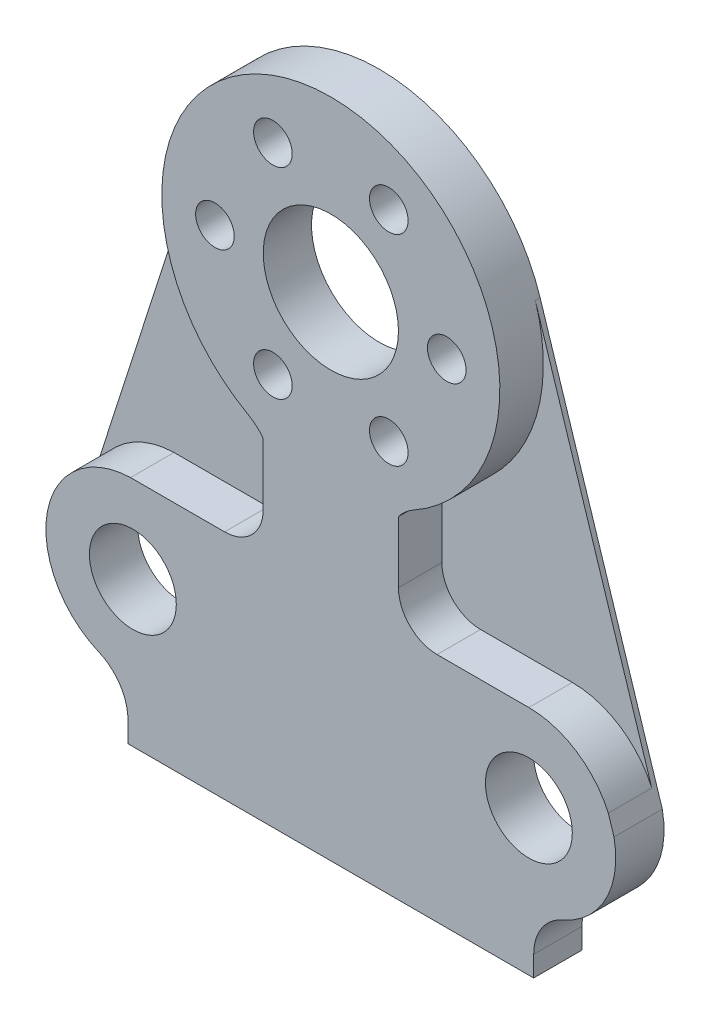
SolidWorks part; units mm, degrees
ref_plane "Front Plane" through (0, 0, 0) normal (0, 0, 1) x (1, 0, 0)
ref_plane "Top Plane" through (0, 0, 0) normal (0, 1, 0) x (1, 0, 0)
ref_plane "Right Plane" through (0, 0, 0) normal (1, 0, 0) x (0, 0, -1)
sketch "Sketch1" plane through (0, 0, 0) normal (0, 0, 1) x (1, 0, 0)
  line L0 (0, 0) -> (0, 50000) construction
  line L1 (-41, -72) -> (41, -72) construction
  line L6 (-41.4693, -54) -> (-22, -54)
  line L8 (21.4626, -54) -> (41, -54)
  line L9 (33.3347, 10.6675) -> (58.6345, -68.391)
  line L11 (-42, -97.7554) -> (-42, -102)
  line L12 (-42, -102) -> (42, -102)
  line L13 (42, -97.7488) -> (42, -102)
  line L14 (-33.3347, 10.6675) -> (-58.1419, -66.4886)
  line L15 (-13.9318, -32.1077) -> (13.9318, -32.1077) construction
  line L16 (-14, -33.2556) -> (-14, -46)
  line L17 (14, -33.2556) -> (14, -46)
  circle A0 centre (0, 0) radius 35
  circle A1 centre (0, 0) radius 14
  circle A2 centre (0, 0) radius 24 construction
  circle A3 centre (24, 0) radius 4
  circle A4 centre (12, -20.7846) radius 4
  circle A5 centre (-12, -20.7846) radius 4
  circle A6 centre (-24, 0) radius 4
  circle A7 centre (-12, 20.7846) radius 4
  circle A8 centre (12, 20.7846) radius 4
  arc A9 (-41.4693, -54) -> (-48.0723, -88.5591) centre (-41, -72) ccw
  arc A10 (48.0714, -88.5528) -> (41, -54) centre (41, -72) ccw
  circle A11 centre (-41, -72) radius 9
  circle A12 centre (41, -72) radius 9
  arc A13 (-42, -97.7554) -> (-48.0723, -88.5591) centre (-52, -97.7554) ccw
  arc A14 (48.0714, -88.5528) -> (42, -97.7488) centre (52, -97.7488) ccw
  arc A16 (-14, -46) -> (-22, -54) centre (-22, -46) cw
  arc A17 (-14, -33.2556) -> (-17.1111, -30.5321) centre (-22, -39.2556) ccw
  arc A18 (14, -33.2556) -> (17.1111, -30.5321) centre (22, -39.2556) cw
  arc A19 (14, -46) -> (22, -54) centre (22, -46) ccw
  point P19 (0, 0)
  point P26 (0, -72)
  point P56 (0, 0)
  point P57 (0, 0)
  point P58 (0, 0)
  point P59 (0, 0)
  dimension "D1" = 8
  dimension "D2" = 70
  dimension "D3" = 48
  dimension "D4" = 28
  dimension "D7" = 82
  dimension "D8" = 18
  dimension "D11" = 18
  dimension "D12" = 10
  dimension "D14" = 8
  dimension "D15" = 10
  dimension "D18" = 18.0061
  dimension "D6" = 28
  dimension "D9" = 84
  dimension "D10" = 30
  dimension "D13" = 72
  dimension "D16" = 33.3347
  dimension "D17" = 58.6345
  dimension "D20" = 33.3347
  dimension "D21" = 32.1077
  dimension "D5" = 6
extrude "Boss-Extrude1" add sketch "Sketch1" along normal blind 10 contours A0 A8 A7 A6 A5 A4 A3 A1 | A19 L17 A18 A0 A17 L16 A16 L6 A9 A13 L11 L12 L13 A14 A10 L9 L8 A12 A11 region at (-0.0066, -73.6365, 0) region at (0, 34.0101, 0)
extrude "Boss-Extrude2" add sketch "Sketch1<3>" along normal blind 1 contours L17 A19 L8 A10 L9 A0 A18 | L16 A17 A0 L14 A9 L6 A16 region at (-33.8245, -36.3541, 0) region at (33.7707, -36.3436, 0)
sketch "Sketch1<3>" plane through (0, 0, 0) normal (0, 0, 1) x (1, 0, 0) same geometry as "Sketch1"
